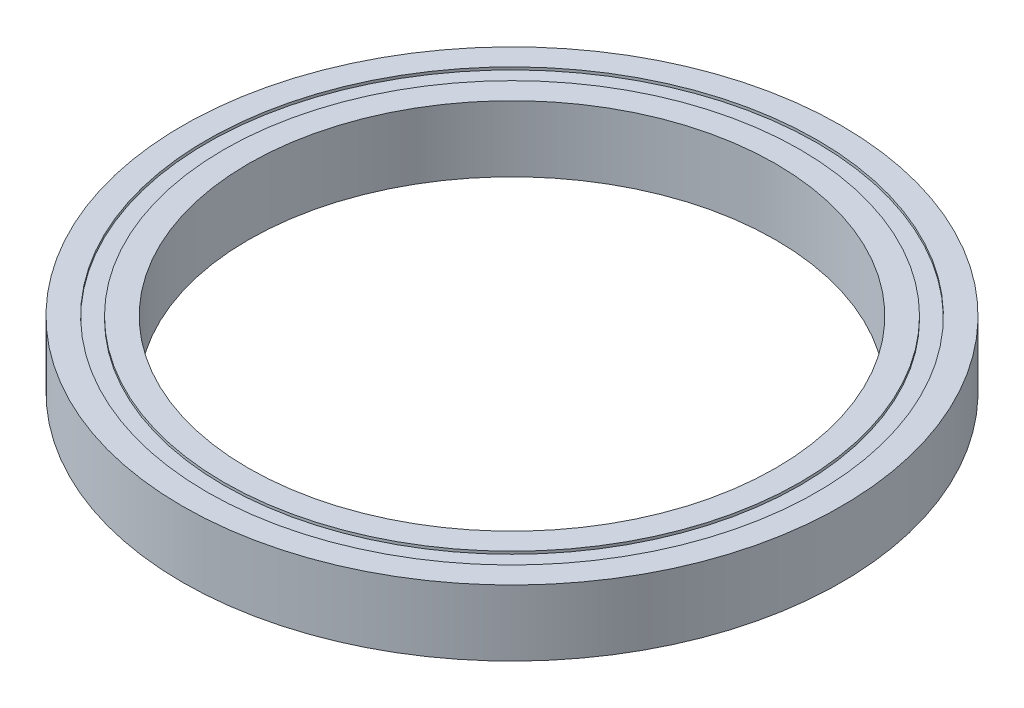
SolidWorks part; units mm, degrees
ref_plane "正面" through (0, 0, 0) normal (0, 0, 1) x (1, 0, 0)
ref_plane "平面" through (0, 0, 0) normal (0, 1, 0) x (1, 0, 0)
ref_plane "右側面" through (0, 0, 0) normal (1, 0, 0) x (0, 0, -1)
sketch "ｽｹｯﾁ1" plane through (0, 0, 0) normal (0, 1, 0) x (1, 0, 0)
  circle A0 centre (0, 0) radius 31.75
  circle A1 centre (0, 0) radius 25.4
  dimension "D1" = 63.5
  dimension "D2" = 50.8
extrude "ﾎﾞｽ - 押し出し1" add sketch "ｽｹｯﾁ1" along normal blind 3.175 and the other way blind 3.175
sketch "ｽｹｯﾁ2" plane through (0, 3.175, 0) normal (0, 1, 0) x (1, 0, 0)
  circle A0 centre (0, 0) radius 27.7622
  circle A1 centre (0, 0) radius 29.3878
  dimension "D1" = 58.7756
  dimension "D2" = 55.5244
extrude "ｶｯﾄ - 押し出し1" cut sketch "ｽｹｯﾁ2" against normal blind 0.254
mirror "ﾐﾗｰ1" about plane through (0, 0, 0) normal (0, 1, 0) of "ｶｯﾄ - 押し出し1"
